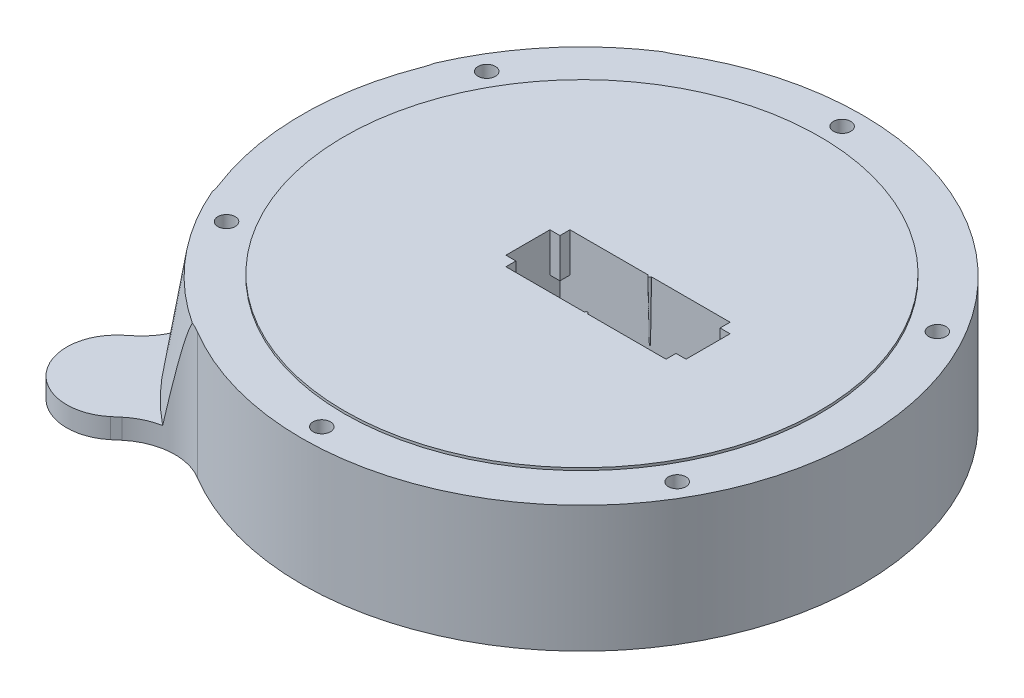
SolidWorks part; units mm, degrees
ref_plane "Front Plane" through (0, 0, 0) normal (0, 0, 1) x (1, 0, 0)
ref_plane "Top Plane" through (0, 0, 0) normal (0, 1, 0) x (1, 0, 0)
ref_plane "Right Plane" through (0, 0, 0) normal (1, 0, 0) x (0, 0, -1)
sketch "Sketch1" plane through (0, 0, 0) normal (0, 1, 0) x (1, 0, 0)
  circle A0 centre (0, 0) radius 88.9
  dimension "D1" = 177.8
extrude "Boss-Extrude1" add sketch "Sketch1" along normal blind 40.894
sketch "Sketch2" plane through (0, 40.894, 0) normal (0, 1, 0) x (1, 0, 0)
  line L0 (-22.4917, 0) -> (22.4917, 0) construction
  line L1 (-17.145, 10.16) -> (40.005, 10.16)
  line L2 (-17.145, 10.16) -> (-17.145, -10.16)
  line L3 (-17.145, -10.16) -> (40.005, -10.16)
  line L4 (40.005, 10.16) -> (40.005, -10.16)
  line L5 (-17.145, 10.16) -> (40.005, -10.16) construction
  line L6 (-17.145, -10.16) -> (40.005, 10.16) construction
  point P0 (11.43, 0)
  dimension "D1" = 20.32
  dimension "D2" = 57.15
  dimension "D3" = 11.43
extrude "Cut-Extrude1" cut sketch "Sketch2" against normal through all
sketch "Sketch3" plane through (0, 0, 0) normal (1, 0, 0) x (0, 0, -1)
  line L0 (0, 22.4917) -> (0, -22.4917) construction
  line L1 (-6.35, 12.7) -> (6.35, 12.7)
  line L2 (-6.35, 12.7) -> (-6.35, 0)
  line L3 (-6.35, 0) -> (6.35, 0)
  line L4 (6.35, 12.7) -> (6.35, 0)
  line L5 (-6.35, 12.7) -> (6.35, 0) construction
  line L6 (-6.35, 0) -> (6.35, 12.7) construction
  line L7 (97.79, 0) -> (-97.79, 0) construction
  point P0 (0, 6.35)
  dimension "D1" = 12.7
extrude "Cut-Extrude2" cut sketch "Sketch3" against normal through all
chamfer "Chamfer1" distance 6.35 angle 45 2 edges at (-52.909, 12.7, 6.35) (-52.909, 12.7, -6.35)
sketch "Sketch4" plane through (0, 40.894, 0) normal (0, 1, 0) x (1, 0, 0)
  line L1 (-17.145, 10.16) -> (-13.97, 10.16)
  line L2 (-17.145, 10.16) -> (-17.145, 6.985)
  line L3 (-17.145, 6.985) -> (-13.97, 6.985)
  line L4 (-13.97, 10.16) -> (-13.97, 6.985)
  line L5 (-17.145, 10.16) -> (-13.97, 6.985) construction
  line L6 (-17.145, 6.985) -> (-13.97, 10.16) construction
  line L7 (-17.145, -10.16) -> (-13.97, -10.16)
  line L8 (-17.145, -10.16) -> (-17.145, -6.985)
  line L9 (-17.145, -6.985) -> (-13.97, -6.985)
  line L10 (-13.97, -10.16) -> (-13.97, -6.985)
  line L11 (-17.145, -10.16) -> (-13.97, -6.985) construction
  line L12 (-17.145, -6.985) -> (-13.97, -10.16) construction
  line L13 (40.005, -10.16) -> (36.83, -10.16)
  line L14 (40.005, -10.16) -> (40.005, -6.985)
  line L15 (40.005, -6.985) -> (36.83, -6.985)
  line L16 (36.83, -10.16) -> (36.83, -6.985)
  line L17 (40.005, -10.16) -> (36.83, -6.985) construction
  line L18 (40.005, -6.985) -> (36.83, -10.16) construction
  line L19 (40.005, 10.16) -> (36.83, 10.16)
  line L20 (40.005, 10.16) -> (40.005, 6.985)
  line L21 (40.005, 6.985) -> (36.83, 6.985)
  line L22 (36.83, 10.16) -> (36.83, 6.985)
  line L23 (40.005, 10.16) -> (36.83, 6.985) construction
  line L24 (40.005, 6.985) -> (36.83, 10.16) construction
  point P4 (-15.5575, 8.5725)
  point P10 (-15.5575, -8.5725)
  point P16 (38.4175, -8.5725)
  point P22 (38.4175, 8.5725)
  dimension "D1" = 3.175
extrude "Boss-Extrude2" add sketch "Sketch4" against normal blind 12.446
sketch "Sketch6" plane through (0, 40.894, 0) normal (0, 1, 0) x (1, 0, 0)
  line L0 (36.83, 10.16) -> (-13.97, 10.16) construction
  line L1 (-13.97, -10.16) -> (36.83, -10.16) construction
  circle A0 centre (11.43, 10.16) radius 0.7937
  circle A1 centre (11.43, -10.16) radius 0.7937
  dimension "D1" = 1.5875
extrude "Boss-Extrude3" add sketch "Sketch6" against normal blind 19.05
chamfer "Chamfer2" distance 0.635 angle 89 2 edges at (11.43, 21.844, 9.3663) (11.43, 21.844, -9.3663) first distance on face at (11.43, 21.844, 9.7631) first distance on face at (11.43, 21.844, -9.7631)
ref_axis "Axis1" through (0, 42.9387, 0) along (0, -1, 0)
sketch "Sketch10" plane through (0, 40.894, 0) normal (0, 1, 0) x (1, 0, 0)
  circle A0 centre (0, 0) radius 88.9
  circle A1 centre (0, 0) radius 75.4062
  circle A2 centre (0, 0) radius 88.9 construction
  dimension "D1" = 150.8125
extrude "Cut-Extrude5" cut sketch "Sketch10" against normal blind 0.7937
sketch "Sketch11" plane through (0, 40.1002, 0) normal (0, 1, 0) x (1, 0, 0)
  line L0 (0, 76.2) -> (0, 88.9) construction
  circle A0 centre (0, 0) radius 76.2 construction
  circle A1 centre (0, 0) radius 88.9 construction
  circle A2 centre (0, 0) radius 88.9 construction
  circle A3 centre (0, 82.55) radius 2.75
  dimension "D1" = 152.4
  dimension "D2" = 5.5
extrude "Cut-Extrude6" cut sketch "Sketch11" against normal blind 6
pattern_circular "CirPattern3" count 6 over 360 about axis through (0, 42.9387, 0) along (0, -1, 0) of "Cut-Extrude6"
sketch "Sketch13" plane through (0, 0, 0) normal (0, -1, 0) x (1, 0, 0)
  line L0 (0, 0) -> (-68.1014, 57.1438) construction
  line L1 (22.4917, 0) -> (-22.4917, 0) construction
  line L2 (-53.9837, 24.5744) -> (-33.5752, 48.8963)
  line L3 (-53.9837, 24.5744) -> (-102.6275, 65.3914)
  line L4 (-33.5752, 48.8963) -> (-82.219, 89.7133)
  line L5 (-102.6275, 65.3914) -> (-82.219, 89.7133)
  line L6 (-53.9837, 24.5744) -> (-82.219, 89.7133) construction
  line L7 (-33.5752, 48.8963) -> (-102.6275, 65.3914) construction
  arc A0 (-88.6729, -6.35) -> (-88.6729, 6.35) centre (0, 0) ccw construction
  dimension "D1" = 40
  dimension "D2" = 31.75
  dimension "D3" = 63.5
extrude "Boss-Extrude6" add sketch "Sketch13" against normal blind 6.35
fillet "Fillet3" radius 15.875 2 edges at (-102.6275, 3.175, 65.3914) (-82.219, 3.175, 89.7133)
fillet "Fillet4" radius 19.05 2 edges at (-56.8025, 3.175, 68.3863) (-77.211, 3.175, 44.0644)
chamfer "Chamfer3" distance 5.715 angle 81 1 edges at (-68.1014, 6.35, 57.1438) first distance on face at (-77.6933, 6.35, 65.1925)
mirror "Mirror2" about plane through (0, 0, 0) normal (0, 0, 1) of "Chamfer3", "Fillet4", "Fillet3", "Boss-Extrude6"
